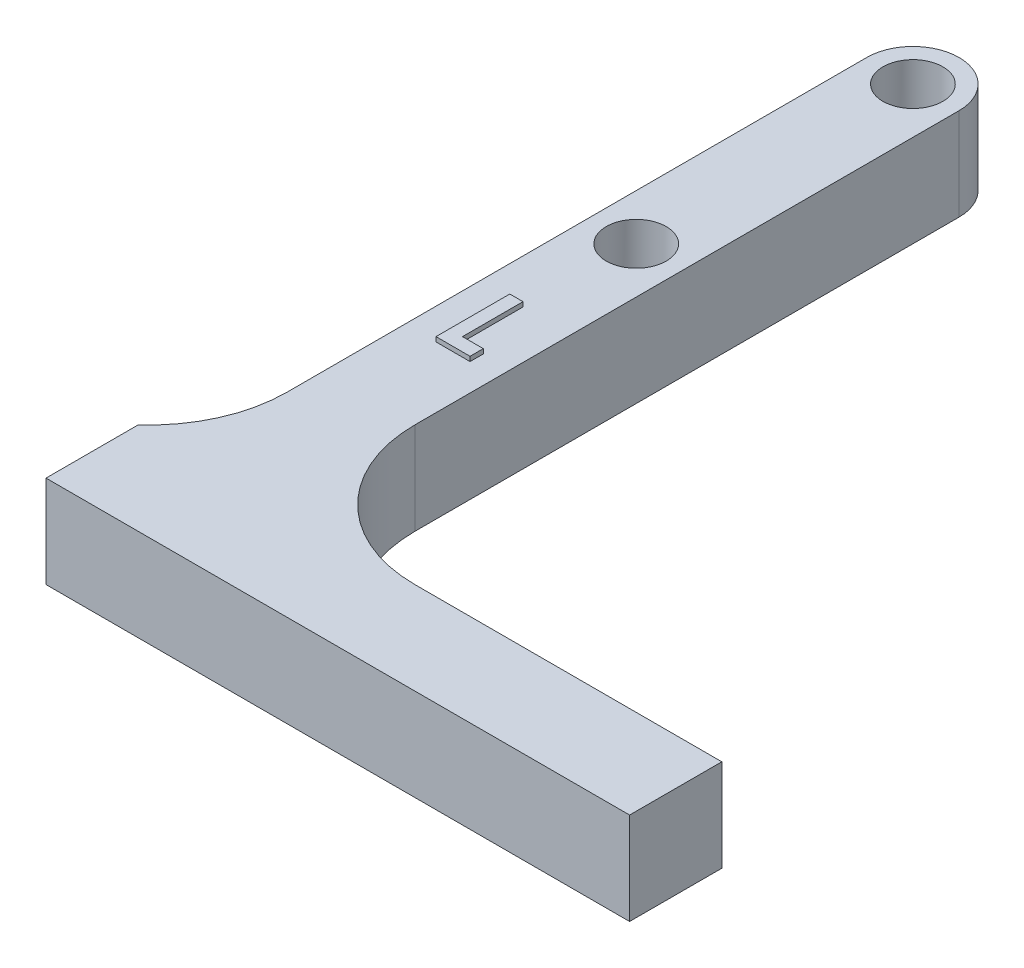
SolidWorks part; units mm, degrees
ref_plane "Front Plane" through (0, 0, 0) normal (0, 0, 1) x (1, 0, 0)
ref_plane "Top Plane" through (0, 0, 0) normal (0, 1, 0) x (1, 0, 0)
ref_plane "Right Plane" through (0, 0, 0) normal (1, 0, 0) x (0, 0, -1)
sketch "Sketch1" plane through (0, 0, 0) normal (0, 1, 0) x (1, 0, 0)
  line L0 (10, 0) -> (10, 10) construction
  line L1 (0, 0) -> (10, 0)
  line L2 (0, 10) -> (0, 84)
  line L3 (0, 84) -> (10, 84) construction
  line L4 (10, 10) -> (10, 84)
  line L5 (10, 0) -> (58.28, 0)
  line L6 (10, 0) -> (10, 10) construction
  line L7 (10, 10) -> (58.28, 10)
  line L8 (58.28, 0) -> (58.28, 10)
  line L9 (0, 10) -> (-5, 10)
  line L10 (0, 10) -> (0, 0) construction
  line L11 (0, 0) -> (-5, 0)
  line L12 (-5, 10) -> (-5, 0)
  line L13 (0, 0) -> (0, 10) construction
  arc A0 (0, 84) -> (10, 84) centre (5, 84) cw
  dimension "D1" = 10
  dimension "D2" = 84
  dimension "D3" = 10
  dimension "D4" = 5
  dimension "D5" = 48.28
extrude "Boss-Extrude1" add sketch "Sketch1" along normal blind 10
sketch "Sketch2" plane through (0, 10, 0) normal (0, 1, 0) x (1, 0, 0)
  circle A0 centre (5, 84) radius 1.5
  circle A1 centre (5, 54) radius 1.5
  dimension "D1" = 3
  dimension "D2" = 30
extrude "Cut-Extrude1" cut sketch "Sketch2" against normal through all
sketch "Sketch4" plane through (0, 10, 0) normal (0, 1, 0) x (1, 0, 0)
  line L0 (0, 33.93) -> (10, 33.93) construction
  line L1 (0, 84) -> (0, 10) construction
  line L2 (10, 10) -> (10, 84) construction
  text T0 "<b>L</b>" font "Century Gothic" height 8
extrude "Boss-Extrude2" add sketch "Sketch4" along normal blind 0.5
sketch "Sketch5" plane through (0, 10, 0) normal (0, 1, 0) x (1, 0, 0)
  circle A0 centre (5, 84) radius 3.25
  circle A1 centre (5, 54) radius 3.25
  dimension "D1" = 6.5
extrude "Cut-Extrude2" cut sketch "Sketch5" against normal offset from surface (5 mm away) 5 up to face at (5, 0, -82.5)
fillet "Fillet1" radius 15 2 edges at (0, 5, -10) (10, 5, -10)
